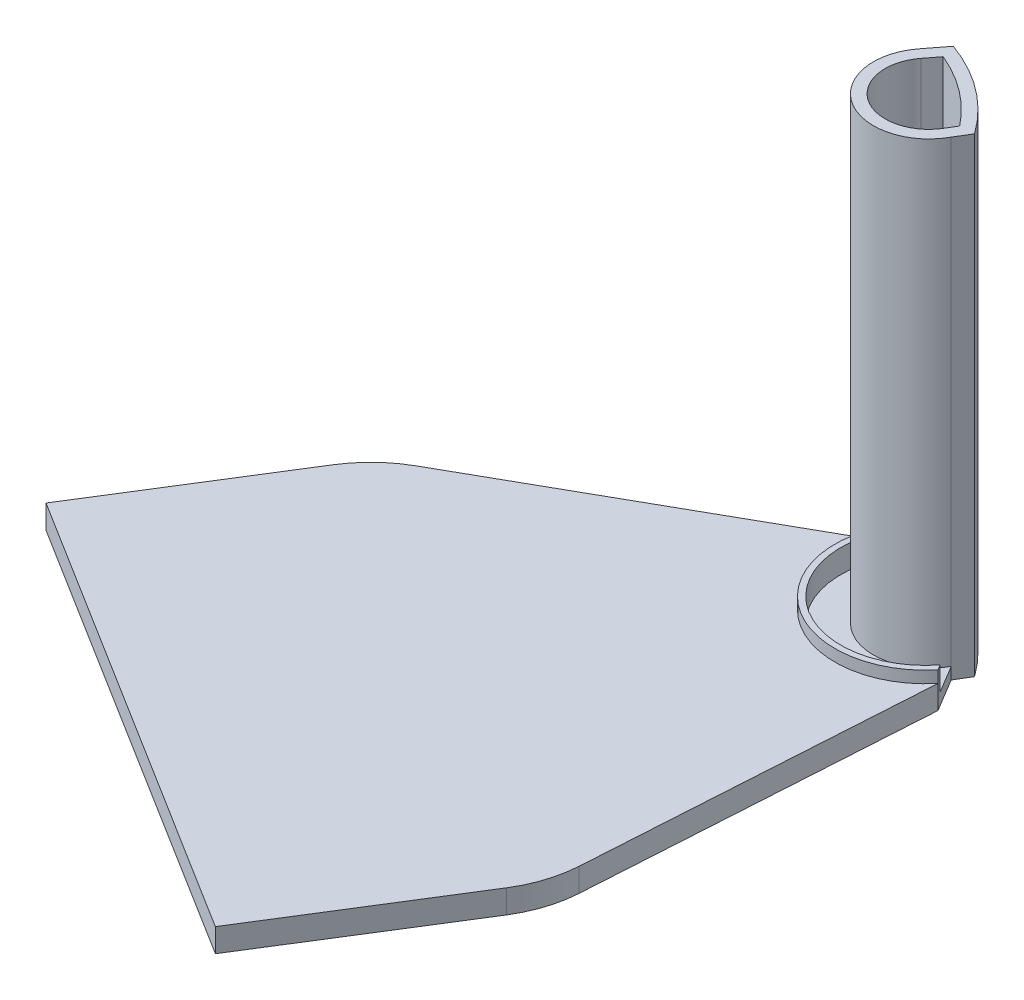
SolidWorks part; units mm, degrees
ref_plane "Alzado" through (0, 0, 0) normal (0, 0, 1) x (1, 0, 0)
ref_plane "Planta" through (0, 0, 0) normal (0, 1, 0) x (1, 0, 0)
ref_plane "Vista lateral" through (0, 0, 0) normal (1, 0, 0) x (0, 0, -1)
sketch "Croquis3" plane through (0, 62.3853, 0) normal (0, 1, 0) x (1, 0, 0)
  line L0 (-8.0359, 0.8886) -> (-4.6602, 0.7384)
  line L1 (3.2253, -4.3817) -> (4.9174, -7.2023)
  arc A3 (-8.0359, 0.8886) -> (4.9174, -7.2023) centre (-1.0355, -2.3184) ccw
  arc A4 (-4.6602, 0.7384) -> (3.2253, -4.3817) centre (-0.9235, -2.1391) ccw
extrude "Saliente-Extruir3" add sketch "Croquis3" along normal blind 1
sketch "Croquis1" plane through (0, 62.3853, 0) normal (0, 1, 0) x (1, 0, 0)
  line L2 (-4.6602, 0.7384) -> (-3.3811, 2.3993)
  line L3 (3.2253, -4.3817) -> (3.9762, -3.1511)
  line L5 (-3.8679, 0.1282) -> (-3.0435, 1.1987)
  line L6 (2.3572, -3.8845) -> (2.7699, -3.2081)
  arc A5 (-4.6602, 0.7384) -> (3.2253, -4.3817) centre (-0.9235, -2.1391) ccw construction
  arc A6 (-4.6602, 0.7384) -> (3.2253, -4.3817) centre (-0.9235, -2.1391) ccw
  arc A9 (2.7699, -3.2081) -> (-3.0435, 1.1987) centre (-8.5312, -12.0786) ccw
  arc A10 (-3.8679, 0.1282) -> (2.3572, -3.8845) centre (-0.9235, -2.1391) ccw
  arc A14 (3.9762, -3.1511) -> (-3.3811, 2.3993) centre (-8.5312, -12.0786) ccw
  dimension "D1" = 1
sketch "Croquis4" plane through (0, 63.3853, 0) normal (0, 1, 0) x (1, 0, 0)
  line L6 (-4.6602, 0.7384) -> (-8.0359, 0.8886) construction
  line L7 (4.9174, -7.2023) -> (3.2253, -4.3817) construction
  line L8 (4.9174, -7.2023) -> (4.643, -6.745)
  line L9 (-7.4938, 0.8645) -> (-8.0359, 0.8886)
  arc A1 (-8.0359, 0.8886) -> (4.9174, -7.2023) centre (-1.0355, -2.3184) ccw
  arc A3 (-8.0359, 0.8886) -> (4.9174, -7.2023) centre (-1.0355, -2.3184) ccw construction
  arc A4 (-7.4938, 0.8645) -> (4.643, -6.745) centre (-1.0355, -2.3184) ccw
  arc A5 (-7.5813, 0.6803) -> (4.643, -6.745) centre (-1.0355, -2.3184) ccw construction
  arc A6 (-8.0359, 0.8886) -> (5.0373, -7.0524) centre (-1.0355, -2.3184) ccw construction
  dimension "D1" = 0.5
extrude "Saliente-Extruir4" add sketch "Croquis4" along normal blind 2
extrude "Saliente-Extruir5" add sketch "Croquis1" along normal blind 40
sketch "Croquis8" plane through (0, 62.3853, 0) normal (0, -1, 0) x (1, 0, 0)
  line L1 (1.6217, 40.6146) -> (-7.9036, 55.8584)
  line L2 (-7.9036, 55.8584) -> (-46.3202, 31.853)
  line L3 (-46.3202, 31.853) -> (-36.9131, 16.7986)
  line L4 (-33.3457, 13.3879) -> (-8.0359, -0.8886)
  line L5 (3.1218, 35.939) -> (4.9174, 7.2023)
  circle A0 centre (-10.4107, 42.2642) radius 7.65
  circle A1 centre (-33.0027, 28.1471) radius 7.65
  arc A2 (3.1218, 35.939) -> (1.6217, 40.6146) centre (-6.8587, 35.3154) ccw
  arc A3 (-33.3457, 13.3879) -> (-36.9131, 16.7986) centre (-28.4327, 22.0978) cw
  arc M11 (4.9174, 7.2023) -> (-8.0359, -0.8886) centre (-1.0355, 2.3184) ccw
  dimension "D1" = 15.3
  dimension "D2" = 15.3
  dimension "D4" = 10
  dimension "D3" = 26.64
  dimension "D5" = 45.3
  dimension "D6" = 9.33
extrude "Saliente-Extruir6" add sketch "Croquis8" against normal blind 2 contours A3 L4 L5 A2 L1 L2 L3 A1 A0 M11 | A0 | A1 region at (-15.4364, 62.3853, 25.2515) region at (-10.4107, 62.3853, 42.2642)
